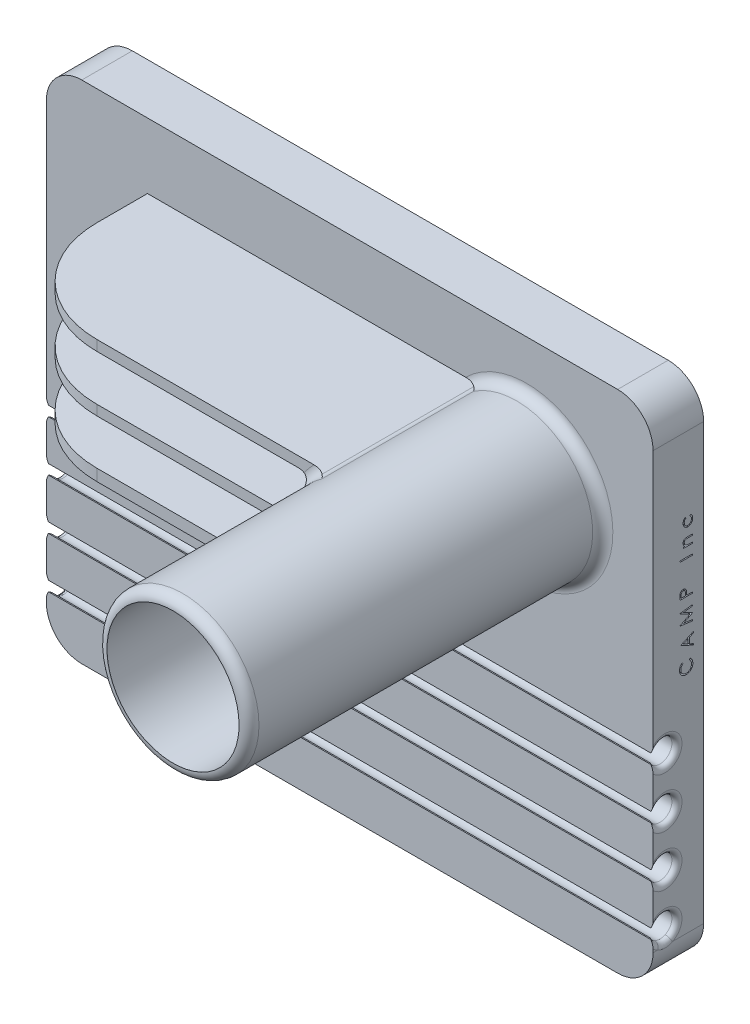
SolidWorks part; units mm, degrees
note: The reader was unsure of these and kept them because the rebuilt part matched: shared geometry of "Sketch2<4>".
ref_plane "Front Plane" through (0, 0, 0) normal (0, 0, 1) x (1, 0, 0)
ref_plane "Top Plane" through (0, 0, 0) normal (0, 1, 0) x (1, 0, 0)
ref_plane "Right Plane" through (0, 0, 0) normal (1, 0, 0) x (0, 0, -1)
sketch "Sketch1" plane through (0, 0, 0) normal (0, 0, 1) x (1, 0, 0)
  line L1 (0, 0) -> (152.4, 0)
  line L2 (0, 0) -> (0, -127)
  line L3 (0, -127) -> (152.4, -127)
  line L4 (152.4, 0) -> (152.4, -127)
  dimension "D1" = 127
  dimension "D2" = 152.4
extrude "Boss-Extrude1" add sketch "Sketch1" along normal blind 12.7 contours L2 L1 L4 L3
sketch "Sketch2" plane through (0, 0, 12.7) normal (0, 0, 1) x (1, 0, 0)
  line L0 (120.65, 0) -> (120.65, -31.75) construction
  line L1 (0, 0) -> (152.4, 0) construction
  line L2 (120.65, -31.75) -> (152.4, -31.75) construction
  line L3 (152.4, 0) -> (152.4, -127) construction
  line L4 (0, -61.2338) -> (25.4, -61.2338) construction
  line L5 (0, 0) -> (0, -127) construction
  line L6 (25.4, -61.2338) -> (25.4, 0) construction
  line L7 (120.65, -31.75) -> (25.4, -31.75) construction
  line L8 (65.2688, -31.75) -> (65.2688, -19.05) construction
  line L9 (65.2688, -44.45) -> (65.2688, -31.75) construction
  line L10 (106.3643, -44.45) -> (25.4, -44.45)
  line L11 (106.3643, -19.05) -> (25.4, -19.05)
  line L12 (25.4, -19.05) -> (25.4, -16.4424)
  line L13 (25.4, -16.4424) -> (109.2024, -16.4424)
  line L14 (25.4, -44.45) -> (25.4, -47.3698)
  line L15 (25.4, -47.3698) -> (109.6322, -47.3698)
  line L16 (109.6322, -47.3698) -> (106.3643, -44.45)
  line L17 (109.2024, -16.4424) -> (106.3643, -19.05)
  line L18 (25.4, -31.75) -> (25.4, -33.0844)
  line L19 (25.4, -33.0844) -> (101.582, -33.0844)
  line L20 (101.582, -33.0844) -> (101.582, -30.4156)
  line L21 (101.582, -30.4156) -> (25.4, -30.6169)
  line L22 (25.4, -30.6169) -> (25.4, -33.0844)
  circle A0 centre (120.65, -31.75) radius 19.1147
sketch "Sketch4" plane through (0, 0, 12.7) normal (0, 0, 1) x (1, 0, 0)
  line L0 (101.5353, -31.75) -> (25.4, -31.75)
  line L1 (120.65, -31.75) -> (25.4, -31.75) construction
  circle A0 centre (120.65, -31.75) radius 19.1147 construction
extrude "Boss-Extrude2" add sketch "Sketch2" along normal blind 88.9 contours A0
sketch "Sketch5" plane through (0, 0, 12.7) normal (0, 0, 1) x (1, 0, 0)
sketch "Sketch6" plane through (0, 0, 12.7) normal (0, 0, 1) x (1, 0, 0)
extrude "Boss-Extrude3" add sketch "Sketch2<4>" along normal blind 38.1 contours L19 L20 L21 L22 | L10 L14 L15 L16 | L13 L17 L11 L12
sketch "Sketch2<4>" plane through (0, 0, 12.7) normal (0, 0, 1) x (1, 0, 0) same geometry as "Sketch2"
sketch "Sketch8" plane through (0, 0, 101.6) normal (0, 0, 1) x (1, 0, 0)
  line L0 (120.7148, -31.6852) -> (120.65, -12.6353) construction
  line L1 (120.7148, -31.6852) -> (139.7647, -31.75) construction
  circle A0 centre (120.7148, -31.6852) radius 16.5838
  arc A1 (109.6322, -47.3698) -> (109.2024, -16.4424) centre (120.65, -31.75) ccw construction
  circle A2 centre (120.65, -31.75) radius 19.1147 construction
extrude "Cut-Extrude1" cut sketch "Sketch8" against normal blind 88.9 contours A0
sketch "Sketch9" plane through (0, 0, 0) normal (-1, 0, 0) x (0, 0, 1)
  line L0 (6.7, -127) -> (6.7, -114.2635) construction
  line L1 (12.7, -127) -> (0, -127) construction
  line L2 (6.7, -114.2635) -> (12.7, -114.2635) construction
  line L3 (12.7, 0) -> (12.7, -127) construction
  line L4 (6.7, -114.2635) -> (6.7, -101.5727) construction
  line L5 (6.7, -101.5727) -> (6.7, -88.8818) construction
  line L6 (6.7, -88.8818) -> (6.7, -76.1909) construction
  line L7 (6.7, -76.1909) -> (12.7, -76.1909) construction
  line L8 (6.7, -88.8818) -> (12.7, -88.8818) construction
  line L9 (6.7, -101.5727) -> (12.7, -101.5727) construction
  circle A0 centre (9.7, -76.1909) radius 3
  circle A1 centre (9.7, -88.8818) radius 3
  circle A3 centre (9.7, -101.5727) radius 3
  circle A4 centre (9.7, -114.2635) radius 3
  point P4 (0, 0)
sketch "Sketch10" plane through (0, 0, 0) normal (-1, 0, 0) x (0, 0, 1)
  line L1 (12.3674, -74.9409) -> (13.0326, -74.9409)
  line L2 (12.3674, -74.9409) -> (12.3674, -77.4409)
  line L3 (12.3674, -77.4409) -> (13.0326, -77.4409)
  line L4 (13.0326, -74.9409) -> (13.0326, -77.4409)
  line L5 (12.3674, -74.9409) -> (13.0326, -77.4409) construction
  line L6 (12.3674, -77.4409) -> (13.0326, -74.9409) construction
  line L7 (12.3674, -87.6318) -> (13.0326, -87.6318)
  line L8 (12.3674, -87.6318) -> (12.3674, -90.1318)
  line L9 (12.3674, -90.1318) -> (13.0326, -90.1318)
  line L10 (13.0326, -87.6318) -> (13.0326, -90.1318)
  line L11 (12.3674, -87.6318) -> (13.0326, -90.1318) construction
  line L12 (12.3674, -90.1318) -> (13.0326, -87.6318) construction
  line L13 (12.3674, -100.3227) -> (13.0326, -100.3227)
  line L14 (12.3674, -100.3227) -> (12.3674, -102.8227)
  line L15 (12.3674, -102.8227) -> (13.0326, -102.8227)
  line L16 (13.0326, -100.3227) -> (13.0326, -102.8227)
  line L17 (12.3674, -100.3227) -> (13.0326, -102.8227) construction
  line L18 (12.3674, -102.8227) -> (13.0326, -100.3227) construction
  line L19 (12.3674, -113.0135) -> (13.0326, -113.0135)
  line L20 (12.3674, -113.0135) -> (12.3674, -115.5135)
  line L21 (12.3674, -115.5135) -> (13.0326, -115.5135)
  line L22 (13.0326, -113.0135) -> (13.0326, -115.5135)
  line L23 (12.3674, -113.0135) -> (13.0326, -115.5135) construction
  line L24 (12.3674, -115.5135) -> (13.0326, -113.0135) construction
  point P0 (12.7, -76.1909)
  point P6 (12.7, -88.8818)
  point P12 (12.7, -101.5727)
  point P18 (12.7, -114.2635)
extrude "Cut-Extrude5" cut sketch "Sketch10" against normal through all both and the other way through all
extrude "Cut-Extrude6" cut sketch "Sketch9" against normal through all both and the other way through all contours A4 | A1 | A0 | A3
fillet "Fillet1" radius 8.89 4 edges at (152.4, 0, 6.35) (152.4, -127, 6.35) (0, -127, 6.35) (0, 0, 6.35)
fillet "Fillet2" radius 25.4 3 edges at (25.4, -17.7462, 50.8) (25.4, -31.8506, 50.8) (25.4, -45.9099, 50.8)
fillet "Fillet3" radius 2.54 13 edges at (109.2024, -16.4424, 31.75) (139.7628, -31.4844, 12.7) (109.6322, -47.3698, 31.75) (107.9143, -46.0038, 50.8) (106.3643, -44.45, 31.75) (103.0315, -39.1634, 12.7) (101.582, -33.0844, 31.75) (101.5353, -31.75, 50.8) (101.582, -30.4156, 31.75) (103.0315, -24.3366, 12.7) (106.3643, -19.05, 31.75) (107.7175, -17.6745, 50.8) (139.7647, -31.75, 101.6)
fillet "Fillet4" radius 1.27 8 edges at (152.4, -76.1909, 6.7) (152.4, -88.8818, 6.7) (152.4, -101.5727, 6.7) (152.4, -114.2635, 6.7) (0, -114.2635, 6.7) (0, -101.5727, 6.7) (0, -88.8818, 6.7) (0, -76.1909, 6.7)
sketch "Sketch11" plane through (152.4, 0, 0) normal (1, 0, 0) x (0, 0, -1)
  text T0 "<r90>C</r>"
  text T1 "<r90>A</r>"
  text T2 "<r90>M</r>"
  text T3 "<r90>P</r>"
  text T4 "<r90>I</r>"
  text T5 "<r90>n</r>"
  text T6 "<r90>c</r>"
  point P1 (-2.7918, -62.0336)
  point P3 (-2.7918, -56.4347)
  point P5 (-2.7918, -51.1024)
  point P7 (0, 0)
  point P8 (-2.7918, -45.2369)
  point P10 (0, 0)
  point P11 (-2.7918, -36.9718)
  point P13 (-2.7918, -34.3056)
  point P15 (0, 0)
  point P16 (-2.7918, -30.0398)
extrude "Cut-Extrude7" cut sketch "Sketch11" against normal blind 1.27
sketch "Sketch13" plane through (0, 0, 12.7) normal (0, 0, 1) x (1, 0, 0)
  line L0 (71.1343, -74.9409) -> (71.1343, -47.3698) construction
  line L1 (0.5134, -74.9409) -> (151.8866, -74.9409) construction
  line L2 (25.4, -47.3698) -> (105.6518, -47.3698) construction
  line L3 (0, -61.1553) -> (152.4, -61.1553) construction
  line L4 (0, -8.89) -> (0, -73.1523) construction
  line L5 (152.4, -8.89) -> (152.4, -73.1523) construction
  line L6 (71.1343, -69.4988) -> (25.4, -69.4988)
  line L7 (25.4, -54.2588) -> (101.6, -54.2588)
  line L8 (101.6, -54.2588) -> (101.6, -69.4988)
  line L9 (101.6, -69.4988) -> (71.1343, -69.4988)
  line L10 (25.4, -54.2588) -> (25.4, -69.4988)
  line L11 (101.6, -58.6958) -> (152.4, -58.6958) construction
  line L12 (25.4, -65.7662) -> (0, -65.7662) construction
sketch "Sketch14" plane through (0, 0, 12.7) normal (0, 0, 1) x (1, 0, 0)
extrude "Boss-Extrude4" add sketch "Sketch13" along normal blind 6.35
sketch "Sketch15" plane through (0, 0, 19.05) normal (0, 0, 1) x (1, 0, 0)
  line L0 (55.6397, -68.2288) -> (55.6397, -69.4988)
  line L1 (26.67, -55.5288) -> (62.865, -55.5288)
  line L2 (26.67, -55.5288) -> (26.67, -68.2288)
  line L3 (26.67, -68.2288) -> (62.865, -68.2288)
  line L4 (62.865, -55.5288) -> (62.865, -68.2288)
  line L5 (65.0698, -55.5288) -> (100.33, -55.5288)
  line L6 (65.0698, -55.5288) -> (65.0698, -68.2288)
  line L7 (65.0698, -68.2288) -> (100.33, -68.2288)
  line L8 (100.33, -55.5288) -> (100.33, -68.2288)
  line L9 (25.4, -69.4988) -> (101.6, -69.4988) construction
  line L10 (88.476, -69.4988) -> (88.476, -68.2288)
  line L11 (25.4, -69.4988) -> (101.6, -69.4988) construction
  line L12 (26.67, -64.0341) -> (25.4, -64.0341)
  line L13 (25.4, -54.2588) -> (25.4, -69.4988) construction
  line L14 (100.33, -59.6944) -> (101.6, -59.6944)
  line L15 (101.6, -69.4988) -> (101.6, -54.2588) construction
extrude "Cut-Extrude9" cut sketch "Sketch15" against normal blind 12.7 contours L8 L5 L6 L7 | L2 L1 L4 L3
sketch "Sketch17" plane through (0, -55.5288, 0) normal (0, -1, 0) x (1, 0, 0)
  line L0 (26.67, 19.05) -> (35.1366, 6.35)
  line L1 (26.67, 6.35) -> (62.865, 6.35) construction
  line L2 (35.1366, 6.35) -> (26.67, 6.35)
  line L3 (26.67, 6.35) -> (26.67, 19.05)
  line L4 (65.0698, 19.05) -> (73.5365, 6.35)
  line L5 (65.0698, 6.35) -> (100.33, 6.35) construction
  line L6 (73.5365, 6.35) -> (65.0698, 6.35)
  line L7 (65.0698, 6.35) -> (65.0698, 19.05) construction
  line L8 (65.0698, 6.35) -> (65.0698, 19.05)
extrude "Boss-Extrude6" add sketch "Sketch17" along normal blind 12.7
